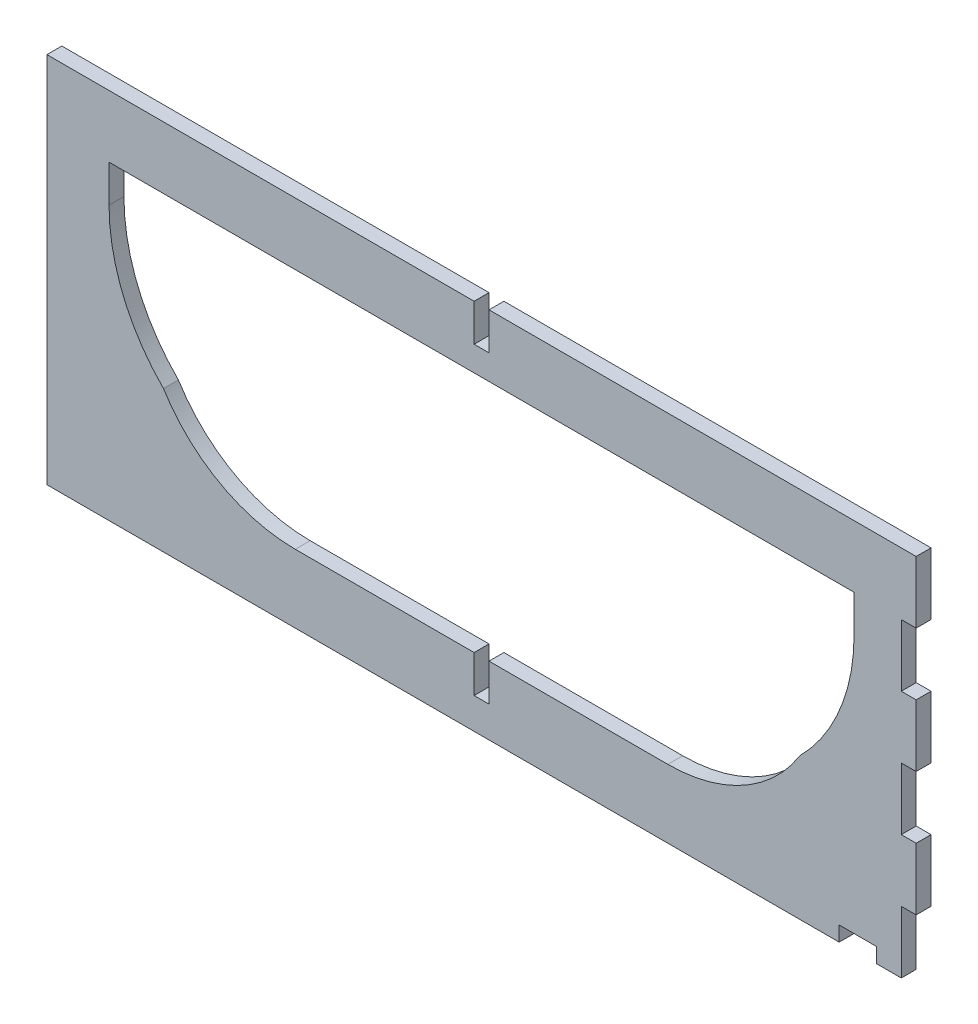
SolidWorks part; units mm, degrees
ref_plane "Front" through (0, 0, 0) normal (0, 0, 1) x (1, 0, 0)
ref_plane "Top" through (0, 0, 0) normal (0, 1, 0) x (1, 0, 0)
ref_plane "Right" through (0, 0, 0) normal (1, 0, 0) x (0, 0, -1)
sketch "Sketch1" plane through (0, 0, 0) normal (0, 0, 1) x (1, 0, 0)
  line L1 (0, 0) -> (-200, 0)
  line L2 (0, 0) -> (0, 150)
  line L4 (-200, 0) -> (-200, 150)
  line L5 (-100, 90) -> (-100, 0) construction
  line L6 (-175, 110) -> (-175, 125)
  line L7 (-25, 110) -> (-25, 125)
  line L9 (-175, 125) -> (-25, 125)
  line L11 (-200, 150) -> (0, 150)
  arc A0 (-153.0972, 57.0313) -> (-46.9028, 57.0312) centre (-100, 90) ccw
  arc A1 (-175, 110) -> (-153.0972, 57.0313) centre (-100, 110) ccw
  arc A2 (-46.9028, 57.0312) -> (-25, 110) centre (-100, 110) ccw
  point P6 (0, 0)
  point P16 (0, 0)
  point P17 (0, 0)
  dimension "D3" = 62.5
  dimension "D4" = 75
  dimension "D1" = 200
  dimension "D2" = 25
  dimension "D5" = 20
  dimension "D6" = 90
  dimension "D7" = 150
extrude "Boss-Extrude1" add sketch "Sketch1" along normal blind 6
sketch "Sketch3" plane through (0, 0, 6) normal (0, 0, 1) x (1, 0, 0)
  line L0 (-200, 150) -> (-200, 0) construction
  line L1 (-100, 27.5) -> (-200, 27.5)
  line L2 (-100, 27.5) -> (-100, 125)
  line L3 (-100, 125) -> (-200, 125)
  line L4 (-200, 27.5) -> (-200, 125)
  line L7 (-25, 125) -> (-175, 125) construction
  arc A0 (-153.0972, 57.0313) -> (-46.9028, 57.0312) centre (-100, 90) ccw construction
extrude "Cut-Extrude1" cut sketch "Sketch3" against normal blind 6
sketch "Sketch4" plane through (0, 0, 6) normal (0, 0, 1) x (1, 0, 0)
  line L0 (-250, 110) -> (-100, 110) construction
  line L1 (-100, 90) -> (-250, 90) construction
  line L2 (-250, 90) -> (-250, 110) construction
  line L3 (-25, 125) -> (0, 125) construction
  line L4 (-200, 27.5) -> (-250, 27.5)
  line L5 (-200, 27.5) -> (-200, 0)
  line L6 (-200, 0) -> (-350, 0)
  line L9 (-350, 0) -> (-350, 150)
  line L11 (-325, 110) -> (-325, 125)
  line L12 (-200, 125) -> (-325, 125)
  line L13 (-200, 125) -> (-200, 150)
  line L14 (-200, 150) -> (-350, 150)
  line L16 (0, 0) -> (0, 150) construction
  line L17 (-325, 125) -> (-350, 125) construction
  line L18 (-200, 0) -> (0, 0) construction
  arc A0 (-325, 110) -> (-303.0972, 57.0312) centre (-250, 110) ccw
  circle A1 centre (-100, 90) radius 62.5 construction
  circle A2 centre (-100, 110) radius 75 construction
  arc A3 (-46.9028, 57.0312) -> (-25, 110) centre (-100, 110) ccw construction
  arc A4 (-100, 27.5) -> (-46.9028, 57.0312) centre (-100, 90) ccw construction
  arc A5 (-303.0972, 57.0312) -> (-250, 27.5) centre (-250, 90) ccw
  point P20 (-350, 1.6583)
  point P36 (-200, 125)
  point P38 (-200, 150)
  point P40 (-25, 125)
  point P42 (0, 0)
  point P43 (0, 0)
  dimension "D1" = 150
  dimension "D2" = 125
  dimension "D4" = 125
  dimension "D3" = 150
extrude "Boss-Extrude3" add sketch "Sketch4" against normal blind 6
sketch "Sketch5" plane through (0, 0, 6) normal (0, 0, 1) x (1, 0, 0)
  line L1 (-178, 150) -> (-172, 150)
  line L2 (-178, 150) -> (-178, 135)
  line L3 (-178, 135) -> (-172, 135)
  line L4 (-172, 150) -> (-172, 135)
  line L5 (-250, 27.5) -> (-100, 27.5) construction
  line L6 (-178, 27.5) -> (-172, 27.5)
  line L7 (-178, 27.5) -> (-178, 12.5)
  line L8 (-178, 12.5) -> (-172, 12.5)
  line L9 (-172, 27.5) -> (-172, 12.5)
  line L10 (0, 150) -> (-350, 150) construction
  point P4 (-177.5407, 147.9373)
  point P12 (-175, 150)
  point P14 (-175, 150)
  dimension "D1" = 6
  dimension "D2" = 15
extrude "Cut-Extrude2" cut sketch "Sketch5" against normal blind 6
sketch "Sketch6" plane through (0, 0, 6) normal (0, 0, 1) x (1, 0, 0)
  line L0 (0, 0) -> (0, 150) construction
  line L1 (0, 125) -> (-6, 125)
  line L2 (0, 125) -> (0, 100)
  line L3 (0, 100) -> (-6, 100)
  line L4 (-6, 125) -> (-6, 100)
  line L5 (0, 150) -> (-172, 150) construction
  dimension "D1" = 25
  dimension "6" = 6
  dimension "D2" = 25
extrude "Cut-Extrude3" cut sketch "Sketch6" against normal blind 6
pattern_linear "LPattern1" count 3 spacing 50 along (0, -1, 0) of "Cut-Extrude3"
sketch "Sketch7" plane through (0, 0, 6) normal (0, 0, 1) x (1, 0, 0)
  line L0 (-350, 0) -> (-6, 0) construction
  line L1 (-16, 0) -> (-31, 0)
  line L2 (-16, 0) -> (-16, 6)
  line L3 (-16, 6) -> (-31, 6)
  line L4 (-31, 0) -> (-31, 6)
  line L5 (-6, 25) -> (-6, 0) construction
  dimension "D1" = 15
  dimension "D2" = 10
  dimension "D3" = 6
extrude "s" cut sketch "Sketch7" against normal through all
